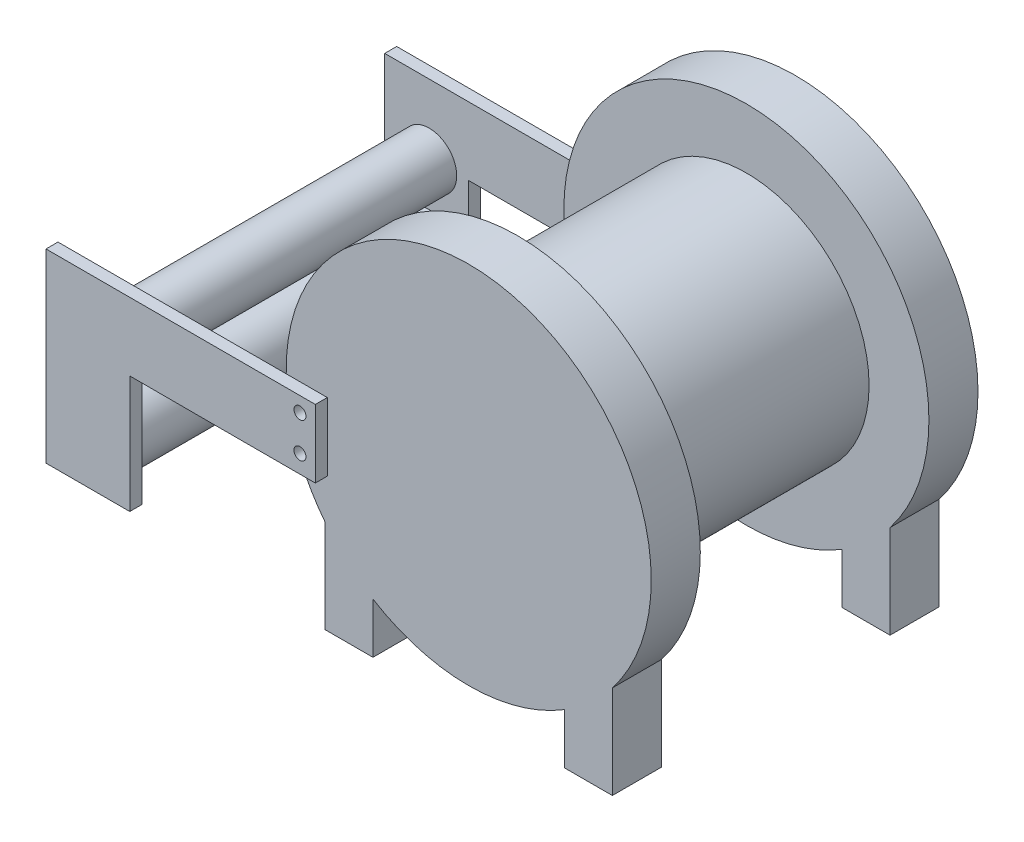
SolidWorks part; units mm, degrees
ref_plane "Front Plane" through (0, 0, 0) normal (0, 0, 1) x (1, 0, 0)
ref_plane "Top Plane" through (0, 0, 0) normal (0, 1, 0) x (1, 0, 0)
ref_plane "Right Plane" through (0, 0, 0) normal (1, 0, 0) x (0, 0, -1)
sketch "Sketch1" plane through (0, 0, 0) normal (0, 0, 1) x (1, 0, 0)
  line L0 (-152.5, 0) -> (152.5, 0) construction
  line L1 (-152.5, 345) -> (152.5, 345) construction
  line L2 (0, 345) -> (0, 0) construction
  line L3 (-152.5, 345) -> (-152.5, 0) construction
  line L4 (152.5, 345) -> (152.5, 0) construction
  line L5 (-152.5, 172) -> (152.5, 172) construction
  line L6 (-100, 345) -> (-100, 0) construction
  line L7 (-120, 172) -> (-120, 0) construction
  line L8 (-80, 172) -> (-80, 0) construction
  line L9 (-120, 77.8923) -> (-120, 0)
  line L10 (-80, 42.1684) -> (-80, 0)
  line L11 (-120, 0) -> (-80, 0)
  line L12 (80, 42.1684) -> (80, 0)
  line L13 (120, 0) -> (80, 0)
  line L14 (120, 77.8923) -> (120, 0)
  arc A0 (-80, 42.1684) -> (80, 42.1684) centre (0, 172) ccw
  arc A1 (120, 77.8923) -> (-120, 77.8923) centre (0, 172) ccw
  circle A2 centre (0, 172) radius 102.5
  point P5 (0, 0)
  point P7 (0, 172)
  dimension "D6" = 205
  dimension "D1" = 345
  dimension "D2" = 152.5
  dimension "D3" = 172
  dimension "D4" = 20
  dimension "D5" = 100
extrude "Boss-Extrude1" add sketch "Sketch1" along normal blind 41 contours L14 A1 L9 L11 L10 A0 L12 L13 A2 | A2 region at (0, 320.0466, 0) region at (0, 172, 0)
extrude "Boss-Extrude2" add sketch "Sketch1<3>" along normal blind 191 from surface contours A2 region at (0, 172, 0) starting at face at (0, 58.0076, 41)
sketch "Sketch1<3>" plane through (0, 0, 0) normal (0, 0, 1) x (1, 0, 0) same geometry as "Sketch1"
extrude "Boss-Extrude3" add sketch "Sketch1<4>" along normal blind 41 from surface contours L14 A1 L9 L11 L10 A0 L12 L13 A2 | A2 region at (0, 320.0466, 0) region at (0, 172, 0) starting at face at (102.5, 172, 232)
sketch "Sketch1<4>" plane through (0, 0, 0) normal (0, 0, 1) x (1, 0, 0) same geometry as "Sketch1"
sketch "Sketch2" plane through (0, 0, 0) normal (0, 0, -1) x (-1, 0, 0)
  line L0 (131, 0) -> (131, 250.0721) construction
  line L1 (0, 172) -> (200.3709, 172) construction
  line L2 (118.1728, 140.45) -> (140.0895, 140.45) construction
  line L3 (118.1728, 168.9) -> (118.1728, 112)
  line L4 (118.1728, 168.9) -> (143.8272, 168.9)
  line L5 (143.8272, 168.9) -> (143.8272, 112)
  line L6 (120, 0) -> (120, 77.8923)
  line L7 (80, 0) -> (120, 0)
  line L8 (80, 42.1684) -> (80, 0)
  line L9 (-80, 0) -> (-80, 42.1684)
  line L10 (-120, 0) -> (-80, 0)
  line L11 (-120, 77.8923) -> (-120, 0)
  line L12 (120, 0) -> (120, 77.8923)
  line L13 (80, 0) -> (120, 0)
  line L14 (80, 42.1684) -> (80, 0)
  line L15 (-80, 0) -> (-80, 42.1684)
  line L16 (-120, 0) -> (-80, 0)
  line L17 (-120, 77.8923) -> (-120, 0)
  line L18 (118.1728, 112) -> (143.8272, 112)
  line L19 (61.7663, 18.0693) -> (144.394, 18.0693) construction
  circle A0 centre (131, 156.4) radius 5
  circle A1 centre (0, 172) radius 102.5
  circle A2 centre (0, 172) radius 102.5
  arc A4 (-80, 42.1684) -> (80, 42.1684) centre (0, 172) ccw
  arc A5 (120, 77.8923) -> (-120, 77.8923) centre (0, 172) ccw
  arc A6 (-80, 42.1684) -> (80, 42.1684) centre (0, 172) ccw
  arc A7 (120, 77.8923) -> (-120, 77.8923) centre (0, 172) ccw
  circle A9 centre (131, 127) radius 5
  point P26 (131, 168.9)
  point P30 (143.8272, 140.45)
  dimension "D6" = 15
  dimension "D9" = 10
  dimension "D3" = 112
  dimension "D4" = 56.9
  dimension "D5" = 12.5
  dimension "D7" = 11
  dimension "D8" = 25.6544
  dimension "D1" = 0
  dimension "D2" = 0
sketch "Sketch3" plane through (0, 0, 0) normal (0, 0, 1) x (1, 0, 0)
  line L0 (-131, 140.45) -> (-306, 140.45) construction
  line L1 (-118.1728, 140.45) -> (-140.0895, 140.45) construction
  line L2 (-131, 0) -> (-131, 250.0721) construction
  line L3 (-131, 112) -> (-306, 112) construction
  line L4 (-118.1728, 112) -> (-143.8272, 112) construction
  line L9 (-118.1728, 112) -> (-118.1728, 168.9)
  line L10 (-118.1728, 168.9) -> (-273.1728, 168.9)
  line L14 (-306, 168.9) -> (-306, 46.9) construction
  line L15 (-131, 168.9) -> (-306, 168.9) construction
  line L16 (-343.1728, 13.9) -> (-273.1728, 13.9)
  line L17 (-273.1728, 112) -> (-273.1728, 13.9)
  line L18 (-118.1728, 112) -> (-273.1728, 112)
  line L19 (-343.1728, 168.9) -> (-118.1728, 168.9)
  line L20 (-343.1728, 13.9) -> (-343.1728, 168.9)
  circle A0 centre (-131, 156.4) radius 5
  circle A1 centre (-131, 127) radius 5
  circle A4 centre (-306, 110.4) radius 23
  circle A5 centre (-306, 46.9) radius 27.5
  dimension "D3" = 55
  dimension "D4" = 46
  dimension "D5" = 122
  dimension "D9" = 10
  dimension "D2" = 114
  dimension "D1" = 175
  dimension "D6" = 70
  dimension "D7" = 225
  dimension "D8" = 155
extrude "Boss-Extrude4" add sketch "Sketch3" against normal blind 10 contours L20 L16 L17 L18 L9 L10 L19 A4 A1 A0 A5 | A5 | A4 region at (-246.421, 123.6361, 0) region at (-306, 110.4, 0) region at (-306, 46.9, 0)
ref_plane "Plane1" through (0, 0, 136.5) normal (0, 0, -1) x (-1, 0, 0)
mirror "Mirror1" about plane through (0, 0, 136.5) normal (0, 0, -1) of "Boss-Extrude4"
extrude "Boss-Extrude5" add sketch "Sketch3<3>" along normal up to surface (273 mm away) from surface contours A4 | A5 region at (-306, 110.4, 0) region at (-306, 46.9, 0) up to face at (-254.6834, 98.1682, 273) starting at face at (-254.6834, 98.1682, 0)
sketch "Sketch3<3>" plane through (0, 0, 0) normal (0, 0, 1) x (1, 0, 0) same geometry as "Sketch3"
sketch "Sketch4" plane through (0, 0, 136.5) normal (0, 0, -1) x (-1, 0, 0)
  circle A0 centre (0, 172) radius 102.5 construction
  circle A1 centre (0, 172) radius 102.5
